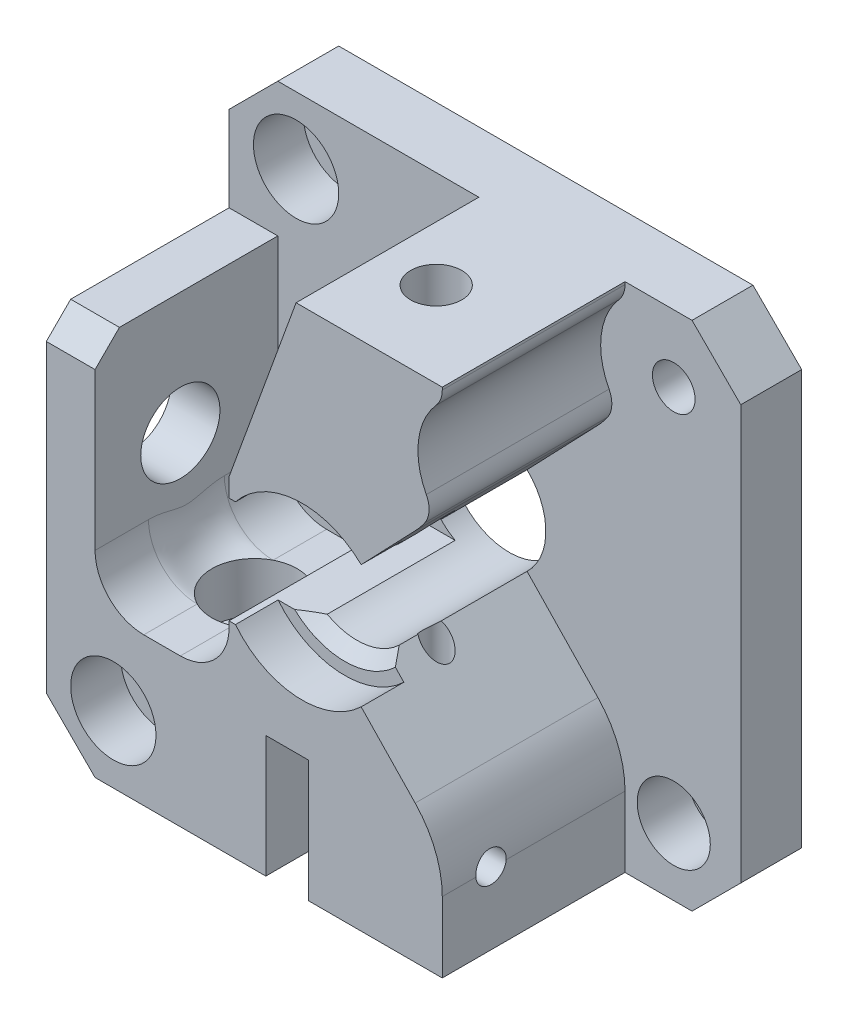
SolidWorks part; units mm, degrees
material "ABS generico"
ref_plane "Piano frontale" through (0, 0, 0) normal (0, 0, 1) x (1, 0, 0)
ref_plane "Piano superiore" through (0, 0, 0) normal (0, 1, 0) x (1, 0, 0)
ref_plane "Piano destro" through (0, 0, 0) normal (1, 0, 0) x (0, 0, -1)
ref_plane "Motor plane" through (0, 0, -20) normal (0, 0, 1) x (1, 0, 0)
sketch "Schizzo1" plane through (0, 0, -20) normal (0, 0, 1) x (1, 0, 0)
  line L1 (15.5, -15.5) -> (-15.5, -15.5) construction
  line L2 (15.5, -15.5) -> (15.5, 15.5) construction
  line L3 (15.5, 15.5) -> (-15.5, 15.5) construction
  line L4 (-15.5, -15.5) -> (-15.5, 15.5) construction
  line L5 (15.5, -15.5) -> (-15.5, 15.5) construction
  line L6 (15.5, 15.5) -> (-15.5, -15.5) construction
  line L7 (21, -21) -> (-21, -21)
  line L8 (21, -21) -> (21, 21)
  line L9 (21, 21) -> (-21, 21)
  line L10 (-21, -21) -> (-21, 21)
  line L11 (21, -21) -> (-21, 21) construction
  line L12 (21, 21) -> (-21, -21) construction
  circle A0 centre (-15.5, 15.5) radius 1.75
  circle A1 centre (15.5, 15.5) radius 1.75
  circle A2 centre (-15.5, -15.5) radius 1.75
  circle A3 centre (15.5, -15.5) radius 1.75
  dimension "D3" = 3.5
  dimension "D1" = 31
  dimension "D2" = 31
  dimension "D5" = 42
  dimension "D6" = 42
extrude "Estrusione-Estrusione1" add sketch "Schizzo1" along normal blind 5
sketch "Schizzo3" plane through (0, 0, -15) normal (0, 0, 1) x (1, 0, 0)
  line L0 (-21, -21) -> (21, -21) construction
  line L1 (11.5, -21) -> (-6, -21)
  line L2 (11.5, -21) -> (11.5, 21)
  line L3 (11.5, 21) -> (-6, 21)
  line L4 (-6, -21) -> (-6, 21)
  line L5 (21, 21) -> (-21, 21) construction
  line L6 (-21, 21) -> (-21, -21) construction
  line L7 (21, -21) -> (21, 21) construction
  dimension "D1" = 15
  dimension "D2" = 9.5
extrude "Estrusione-Estrusione4" add sketch "Schizzo3" along normal blind 15
sketch "Schizzo4" plane through (0, 0, 0) normal (0, 0, 1) x (1, 0, 0)
  circle A0 centre (0, 0) radius 5
  dimension "D1" = 10
extrude "Taglio-Estrusione1" cut sketch "Schizzo4" against normal through all
ref_plane "Piano3" through (4, 0, 0) normal (1, 0, 0) x (0, 0, -1)
sketch "Schizzo6" plane through (0, -21, 0) normal (0, -1, 0) x (1, 0, 0)
  line L0 (11.5, -7) -> (-6, -7) construction
  line L2 (-6, 0) -> (-6, -15) construction
  line L3 (4, -11) -> (4, 11) construction
  line L4 (4, -2.5823) -> (4, -27.3722) construction
  line L9 (23.1, -20) -> (-23.1, -20) construction
  circle A0 centre (4, -7) radius 1.1
  point P10 (4, -7)
  dimension "D1" = 2.2
  dimension "D2" = 13
extrude "Taglio-Estrusione3" cut sketch "Schizzo6" against normal through all
sketch "Schizzo7" plane through (0, 0, 0) normal (0, 0, 1) x (1, 0, 0)
  line L0 (11.5, 0) -> (-6, 0) construction
  line L1 (11.5, -21) -> (11.5, 21) construction
  line L2 (-6, 21) -> (-6, -21) construction
  line L3 (11.5, 12) -> (0, 0)
  line L4 (11.5, 12) -> (11.5, -12)
  line L5 (11.5, -12) -> (0, 0)
  dimension "D1" = 12
extrude "Taglio-Estrusione4" cut sketch "Schizzo7" against normal blind 15
fillet "Raccordo2" radius 8 1 edges at (11.5, 12, -7.5)
fillet "Raccordo3" radius 8 1 edges at (11.5, -12, -7.5)
chamfer "Smusso1" distance 4 angle 45 4 edges at (21, -21, -17.5) (-21, -21, -17.5) (-21, 21, -17.5) (21, 21, -17.5)
sketch "Schizzo22" plane through (11.5, 0, 0) normal (1, 0, 0) x (0, 0, -1)
  line L0 (15, -17) -> (15, 17) construction
  point P0 (4, -15.1119)
  dimension "D1" = 11
hole_wizard "Foro filettato M3-2" positions "Schizzo24" profile "Schizzo23" tap size "M3" standard "ISO"
sketch "Schizzo24" plane through (11.5, 0, 0) normal (1, 0, 0) x (0, 0, -1)
  point P0 (4, -15.1119)
sketch "Schizzo23" plane through (11.5, -15.1119, -4) normal (0, 1, 0) x (0, 0, -1)
  line L0 (0, 0) -> (0, 12.7511)
  line L1 (0, 12.7511) -> (1.25, 12)
  line L2 (1.25, 12) -> (1.25, 0)
  line L5 (1.25, 0) -> (0, 0)
  line L10 (0, 12.7511) -> (-1.25, 12) construction
  line L11 (0, -6.35) -> (0, 107.95) construction
  dimension "Tap Drill Dia." = 2.5
  dimension "Tap Drill Depth" = 12
  dimension "Drill Angle" = 118
cosmetic thread "Filettatura del foro2" parameters "D1"=6, "D2"=3
sketch "Schizzo28" plane through (0, 0, -15) normal (0, 0, 1) x (1, 0, 0)
  line L1 (-21, 0) -> (21, 0) construction
  line L2 (-21, 17) -> (-21, -17) construction
  line L3 (21, -17) -> (21, 17) construction
  line L4 (-21, -10) -> (-21, 10)
  line L6 (-21, 10) -> (-17, 10)
  line L7 (-17, 10) -> (-17, -10)
  line L8 (-21, -10) -> (-17, -10)
  point P13 (-17, 0)
  dimension "D1" = 4
  dimension "D2" = 10
extrude "Estrusione-Estrusione5" add sketch "Schizzo28" along normal blind 15
sketch "Schizzo29" plane through (0, 0, -15) normal (0, 0, 1) x (1, 0, 0)
  circle A0 centre (-15.5, 15.5) radius 3.5
  circle A2 centre (15.5, -15.5) radius 3
  dimension "D1" = 7
extrude "Taglio-Estrusione6" cut sketch "Schizzo29" against normal blind 4.1
chamfer "Smusso3" distance 5.5 angle 70 1 edges first distance on face at (5.1, 21, -7)
sketch "Schizzo30" plane through (-21, 0, 0) normal (-1, 0, 0) x (0, 0, 1)
  line L0 (0, 0) -> (-20, 0) construction
  line L1 (0, 10) -> (0, -10) construction
  line L2 (-20, -23.1) -> (-20, 23.1) construction
  circle A0 centre (-7, 0) radius 3.25
  dimension "D1" = 6.5
  dimension "D2" = 7
extrude "Taglio-Estrusione7" cut sketch "Schizzo30" against normal blind 4
chamfer "Smusso4" distance 2 angle 45 1 edges at (-19, 10, 0)
hole_wizard "Foro filettato M5-1" positions "Schizzo3D1" profile "Schizzo31" tap size "M5" standard "ISO"
sketch3d "Schizzo3D1"
  line L0 (4, 21, -7) -> (4, 3.6099, -7) construction
  point P0 (4, 21, -7)
sketch "Schizzo31" plane through (4, 21, -7) normal (1, 0, 0) x (0, 0, 1)
  line L0 (0, 0) -> (0, 6.2618)
  line L1 (0, 6.2618) -> (2.1, 5)
  line L2 (2.1, 5) -> (2.1, 0)
  line L5 (2.1, 0) -> (0, 0)
  line L10 (0, 6.2618) -> (-2.1, 5) construction
  line L11 (0, -6.35) -> (0, 107.95) construction
  dimension "Tap Drill Dia." = 4.2
  dimension "Tap Drill Depth" = 5
  dimension "Drill Angle" = 118
cosmetic thread "Filettatura del foro3" parameters "D1"=5, "D2"=5
sketch "Schizzo32" plane through (0, 0, 0) normal (0, 0, 1) x (1, 0, 0)
  circle A0 centre (0, 0) radius 7
  dimension "D1" = 14
extrude "Taglio-Estrusione8" cut sketch "Schizzo32" against normal blind 3.5
sketch "Schizzo33" plane through (0, 0, -20) normal (0, 0, -1) x (-1, 0, 0)
  circle A0 centre (0, 0) radius 12
  dimension "D1" = 24
extrude "Taglio-Estrusione9" cut sketch "Schizzo33" against normal blind 3
sketch "Schizzo34" plane through (0, 0, 0) normal (0, 0, 1) x (1, 0, 0)
  circle A0 centre (15.5, 15.5) radius 6
  dimension "D1" = 12
extrude "Taglio-Estrusione10" cut sketch "Schizzo34" along direction (0, 0, 1) on the side against the normal blind 15
fillet "Raccordo4" radius 2 1 edges at (11.5, 19.9721, -7.5)
fillet "Raccordo5" radius 2 1 edges at (10.7505, 11.8336, -7.5)
chamfer "Smusso5" distance 1 angle 45 1 edges at (-5, 0, -3.5)
sketch "Schizzo35" plane through (0, 0, -15) normal (0, 0, 1) x (1, 0, 0)
  line L0 (-17, -8.8557) -> (-6, -8.8557)
  line L1 (-17, -10) -> (-17, 10) construction
  line L3 (-6, -8.8557) -> (-6, -21)
  line L4 (-6, -21) -> (-17, -21)
  line L5 (-17, -21) -> (-21, -17)
  line L6 (-21, -17) -> (-21, -10)
  line L7 (-21, -10) -> (-17, -10)
  line L8 (-17, -10) -> (-17, -8.8557)
  line L9 (-6, 5.8889) -> (-6, -21) construction
extrude "Estrusione-Estrusione6" add sketch "Schizzo35" along normal up to vertex (15 mm away) up to point (-6, -3.6056, 0)
sketch "Schizzo36" plane through (0, 0, 0) normal (0, 0, 1) x (1, 0, 0)
  circle A0 centre (-15.5, -15.5) radius 1.75
extrude "Taglio-Estrusione11" cut sketch "Schizzo36" against normal through all
sketch "Schizzo37" plane through (0, -8.8557, 0) normal (0, 1, 0) x (1, 0, 0)
  line L0 (-17, 7.5) -> (-5.8125, 7.5) construction
  line L1 (-17, 0) -> (-17, 15) construction
  line L2 (-11.4063, 7.5) -> (-11.4063, 0) construction
  line L3 (-6, 0) -> (-17, 0) construction
  circle A0 centre (-11.4063, 7.5) radius 2.1
  dimension "D1" = 4.2
extrude "Taglio-Estrusione12" cut sketch "Schizzo37" against normal through all
sketch "Schizzo38" plane through (0, 0, 0) normal (0, 0, 1) x (1, 0, 0)
  circle A0 centre (-15.5, -15.5) radius 3.5
  dimension "D1" = 7
extrude "Taglio-Estrusione13" cut sketch "Schizzo38" against normal blind 4.1
sketch "Schizzo39" plane through (0, -8.8557, 0) normal (0, 1, 0) x (1, 0, 0)
  circle A0 centre (-11.4063, 7.5) radius 3.5
  dimension "D1" = 7
extrude "Taglio-Estrusione14" cut sketch "Schizzo39" against normal blind 4.1
fillet "Raccordo6" radius 4 2 edges at (-6, -8.8557, -7.5) (-17, -8.8557, -7.5)
sketch "Schizzo40" plane through (0, -21, 0) normal (0, -1, 0) x (1, 0, 0)
  line L0 (4, -11) -> (4, 11) construction
  line L1 (23.1, -20) -> (-23.1, -20) construction
  circle A0 centre (4, -15) radius 1
  circle A1 centre (4, -7) radius 1.1 construction
  dimension "D1" = 2
  dimension "D3" = 8
  dimension "D2" = 5
extrude "Taglio-Estrusione15" cut sketch "Schizzo40" against normal blind 6
sketch "Sketch1" plane through (0, 0, 0) normal (0, 0, 1) x (1, 0, 0)
  line L0 (-7.0211, 4.3623) -> (-7.0211, -4.3623)
  line L1 (-7.0211, -4.3623) -> (-2.0805, -4.3623)
  line L3 (-7.0211, 4.3623) -> (-2.0805, 4.3623)
  line L7 (-2.0805, 4.3623) -> (-2.0805, -4.3623)
  point P0 (-6, 0)
extrude "Cut-Extrude1" cut sketch "Sketch1" against normal up to surface (15 mm away) up to face at (-12, 15.5, -15)
sketch "Sketch2" plane through (0, -21, 0) normal (0, -1, 0) x (1, 0, 0)
  line L0 (11.4431, 6.0783) -> (11.4431, -22.853) construction
  line L1 (-2.9851, 0) -> (0.5149, 0)
  line L2 (-2.9851, 0) -> (-2.9851, -7.5)
  line L3 (-2.9851, -7.5) -> (0.5149, -7.5)
  line L4 (0.5149, 0) -> (0.5149, -7.5)
  line L5 (-2.9851, 0) -> (0.5149, -7.5) construction
  line L6 (-2.9851, -7.5) -> (0.5149, 0) construction
  point P0 (-1.2351, -3.75)
  line M7 (11.5, 0) -> (-17, 0)
  dimension "D1" = 3.5
  dimension "D2" = 7.5
extrude "Cut-Extrude2" cut sketch "Sketch2" against normal blind 10 contours L4 L2 L3 M7 region at (-1.2351, -21, -3.75)
